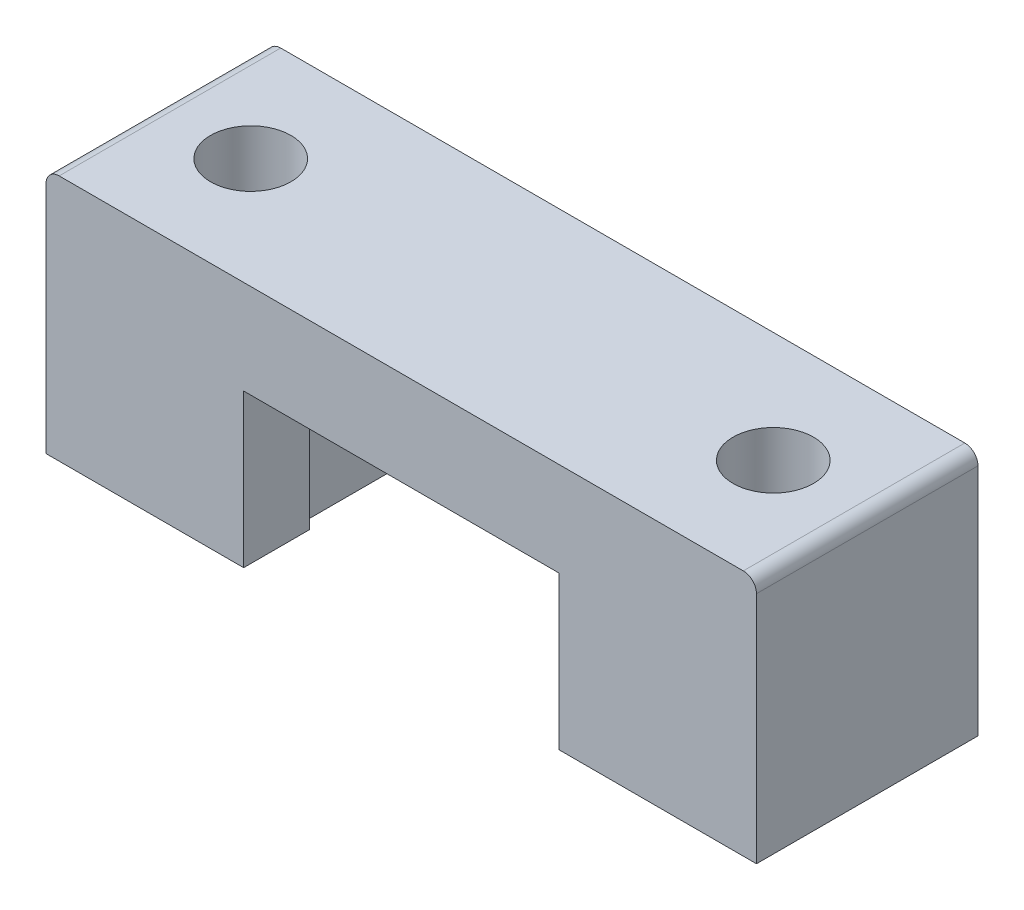
SolidWorks part; units mm, degrees
ref_plane "Front Plane" through (0, 0, 0) normal (0, 0, 1) x (1, 0, 0)
ref_plane "Top Plane" through (0, 0, 0) normal (0, 1, 0) x (1, 0, 0)
ref_plane "Right Plane" through (0, 0, 0) normal (1, 0, 0) x (0, 0, -1)
sketch "Sketch1" plane through (0, 0, 0) normal (0, 1, 0) x (1, 0, 0)
  line L0 (0, 0) -> (0, -6)
  line L1 (0, -6) -> (0.375, -6)
  line L2 (0.375, -6) -> (0.375, -8.54)
  line L3 (0.375, -8.54) -> (12.525, -8.54)
  line L4 (12.525, -8.54) -> (12.525, -6)
  line L5 (12.525, -6) -> (12.9, -6)
  line L6 (12.9, -6) -> (12.9, 0)
  line L7 (12.9, 0) -> (0, 0)
  line L8 (0, 0) -> (-7.245, 0)
  line L9 (-7.245, 0) -> (-7.245, -8.54)
  line L10 (-7.245, -8.54) -> (0.375, -8.54)
  line L11 (12.9, 0) -> (20.145, 0)
  line L12 (20.145, 0) -> (20.145, -8.54)
  line L13 (20.145, -8.54) -> (12.525, -8.54)
  circle A0 centre (-3.6225, -4.27) radius 1.55
  circle A1 centre (16.5225, -4.27) radius 1.55
  point P19 (20.145, -4.27)
  point P21 (-3.6225, 0)
  point P23 (16.5225, 0)
  dimension "D7" = 3.1
  dimension "D1" = 2.54
  dimension "D2" = 6
  dimension "D3" = 12.9
  dimension "D4" = 0.375
  dimension "D5" = 0.375
  dimension "D6" = 7.62
extrude "Boss-Extrude1" add sketch "Sketch1" along normal blind 9.525 contours L8 L10 L2 L1 L0 | L6 L7 L0 L1 L2 L3 L4 L5 | L11 L6 L5 L4 L13 | L8 L9 L10 | L11 L13 L12 region at (6.45, 0, 4.2172) region at (-0.1145, 0, 3) region at (16.5225, 0, 0.1145)
extrude "Cut-Extrude1" cut sketch "Sketch1<4>" along normal blind 5.9 contours L6 L7 L0 L1 L2 L3 L4 L5 region at (6.45, 0, 4.2172)
sketch "Sketch1<4>" plane through (0, 0, 0) normal (0, 1, 0) x (1, 0, 0) same geometry as "Sketch1"
fillet "Fillet1" radius 0.508 2 edges at (-7.245, 9.525, 4.27) (20.145, 9.525, 4.27)
